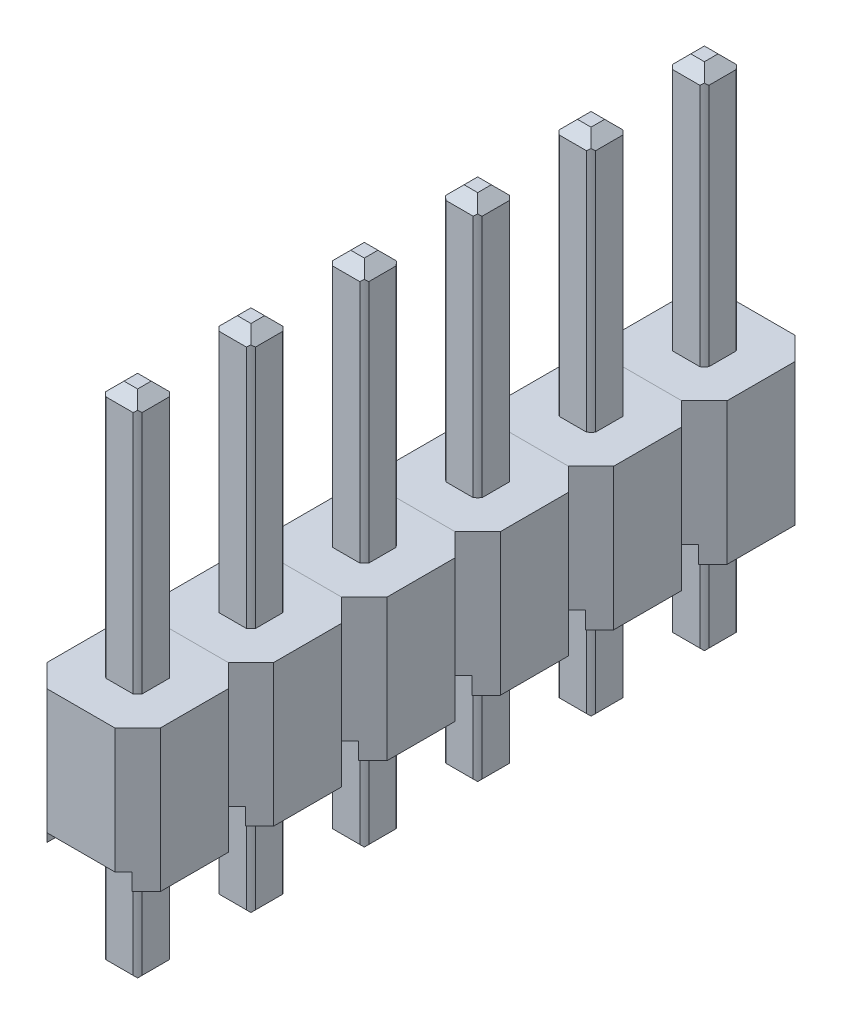
SolidWorks part; units mm, degrees
ref_plane "Front Plane" through (0, 0, 0) normal (0, 0, 1) x (1, 0, 0)
ref_plane "Top Plane" through (0, 0, 0) normal (0, 1, 0) x (1, 0, 0)
ref_plane "Right Plane" through (0, 0, 0) normal (1, 0, 0) x (0, 0, -1)
sketch "Sketch3" plane through (0, 0, 0) normal (0, 1, 0) x (1, 0, 0)
  line L1 (-1, -1) -> (1, -1)
  line L2 (-1, -1) -> (-1, 1)
  line L3 (-1, 1) -> (1, 1)
  line L4 (1, -1) -> (1, 1)
  line L5 (-1, -1) -> (1, 1) construction
  line L6 (-1, 1) -> (1, -1) construction
  point P0 (0, 0)
  dimension "D1" = 2
extrude "Boss-Extrude3" add sketch "Sketch3" along normal blind 2.5
sketch "Sketch4" plane through (0, 0, 1) normal (0, 0, 1) x (1, 0, 0)
  line L0 (-1, 0) -> (1, 0) construction
  line L1 (-0.75, 0) -> (0.75, 0)
  line L2 (-0.75, 0) -> (-0.75, 0.3)
  line L3 (-0.75, 0.3) -> (0.75, 0.3)
  line L4 (0.75, 0) -> (0.75, 0.3)
  line L5 (1, 2.5) -> (1, 0) construction
  line L6 (-1, 2.5) -> (-1, 0) construction
  dimension "D1" = 0.25
  dimension "D2" = 0.25
  dimension "D3" = 0.3
extrude "Cut-Extrude1" cut sketch "Sketch4" against normal through all
chamfer "Chamfer1" distance 0.4 angle 45 4 edges at (-1, 1.25, 1) (-1, 1.25, -1) (1, 1.25, -1) (1, 1.25, 1)
sketch "Sketch5" plane through (0, 0, 0) normal (0, 1, 0) x (1, 0, 0)
  line L1 (-0.24, -0.32) -> (0.24, -0.32)
  line L2 (-0.32, -0.24) -> (-0.32, 0.24)
  line L3 (-0.24, 0.32) -> (0.24, 0.32)
  line L4 (0.32, -0.24) -> (0.32, 0.24)
  line L5 (-0.2828, -0.2828) -> (0.2828, 0.2828) construction
  line L6 (-0.2828, 0.2828) -> (0.2828, -0.2828) construction
  arc A0 (0.32, 0.24) -> (0.24, 0.32) centre (0, 0) ccw
  arc A1 (-0.24, 0.32) -> (-0.32, 0.24) centre (0, 0) ccw
  arc A2 (-0.32, -0.24) -> (-0.24, -0.32) centre (0, 0) ccw
  arc A3 (0.24, -0.32) -> (0.32, -0.24) centre (0, 0) ccw
  dimension "D1" = 0.8
extrude "Boss-Extrude4" add sketch "Sketch5" along normal blind 7 and the other way blind 2
chamfer "Chamfer2" distance 0.2 angle 45 8 edges at (0.32, -2, 0) (0, -2, -0.32) (-0.32, -2, 0) (0, -2, 0.32) (0, 7, 0.32) (-0.32, 7, 0) (0, 7, -0.32) (0.32, 7, 0)
pattern_linear "LPattern1" count 6 spacing 2 along (0, 0, -1) of bodies 105
